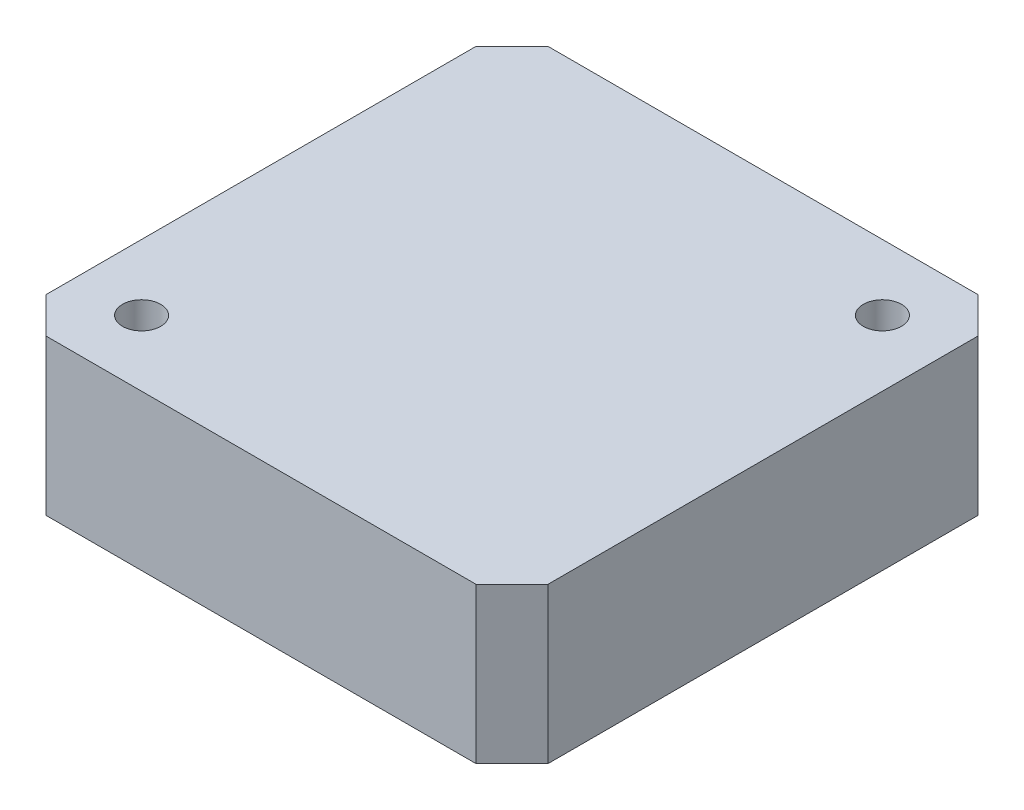
SolidWorks part; units mm, degrees
ref_plane "Alzado" through (0, 0, 0) normal (0, 0, 1) x (1, 0, 0)
ref_plane "Planta" through (0, 0, 0) normal (0, 1, 0) x (1, 0, 0)
ref_plane "Vista lateral" through (0, 0, 0) normal (1, 0, 0) x (0, 0, -1)
sketch "Croquis1" plane through (0, 0, 0) normal (0, 1, 0) x (1, 0, 0)
  line L1 (21, -21) -> (-21, -21)
  line L2 (21, -21) -> (21, 21)
  line L3 (21, 21) -> (-21, 21)
  line L4 (-21, -21) -> (-21, 21)
  line L5 (21, -21) -> (-21, 21) construction
  line L6 (21, 21) -> (-21, -21) construction
  point P0 (0, 0)
  dimension "D1" = 42
  dimension "D2" = 42
extrude "Saliente-Extruir1" add sketch "Croquis1" along normal blind 13
sketch "Croquis2" plane through (21, 0, 0) normal (1, 0, 0) x (0, 0, -1)
  line L1 (-24, -3) -> (-24, -6)
  line L2 (-24, -6) -> (27, -6)
  line L6 (27, 22.5) -> (24, 22.5)
  line L8 (27, 22.5) -> (27, -6)
  line L9 (-24, -3) -> (24, -3)
  line L10 (24, -3) -> (24, 22.5)
  line L11 (-21, 0) -> (21, 0) construction
  line L12 (-21, 13) -> (-21, 0) construction
  line L13 (21, 13) -> (21, 0) construction
  dimension "D1" = 3
  dimension "D2" = 3
  dimension "D3" = 3
  dimension "D4" = 3
  dimension "D5" = 28.5
  dimension "D6" = 3
extrude "Saliente-Extruir2" [suppressed] add sketch "Croquis2" against normal blind 42 separate body
sketch "Croquis3" [suppressed] plane through (0, 0, -24) normal (0, 0, 1) x (1, 0, 0)
  line L0 (-21, 22.5) -> (-21, -3) construction
  line L1 (-21, 15) -> (21, 15) construction
  circle A0 centre (-16, 19) radius 1.75
  circle A1 centre (-16, 19) radius 3.25 construction
  dimension "D1" = 3.5
  dimension "D4" = 6.5
  dimension "D2" = 5
  dimension "D3" = 4
extrude "Cortar-Extruir1" [suppressed] cut sketch "Croquis3" against normal through all
chamfer "Chaflán1" distance 3 angle 45 4 edges at (-21, 6.5, -21) (21, 6.5, -21) (21, 6.5, 21) (-21, 6.5, 21)
sketch "Croquis4" plane through (0, 13, 0) normal (0, 1, 0) x (1, 0, 0)
  line L8 (18, 15.5) -> (-18, 15.5)
  line L9 (15.5, 15.5) -> (-15.5, 15.5) construction
  line L11 (-18, -15.5) -> (18, -15.5)
  line L12 (-15.5, -15.5) -> (15.5, -15.5) construction
  line L14 (-15.5, 18) -> (-15.5, -18)
  line L15 (-15.5, 15.5) -> (-15.5, -15.5) construction
  line L17 (15.5, -18) -> (15.5, 18)
  line L18 (15.5, -15.5) -> (15.5, 15.5) construction
  circle A0 centre (15.5, 15.5) radius 1.6
  circle A1 centre (-15.5, -15.5) radius 1.6
  dimension "D5" = 3.2
  dimension "D1" = 5.5
  dimension "D2" = 5.5
  dimension "D3" = 5.5
  dimension "D4" = 5.5
extrude "Cortar-Extruir2" cut sketch "Croquis4" against normal through all
